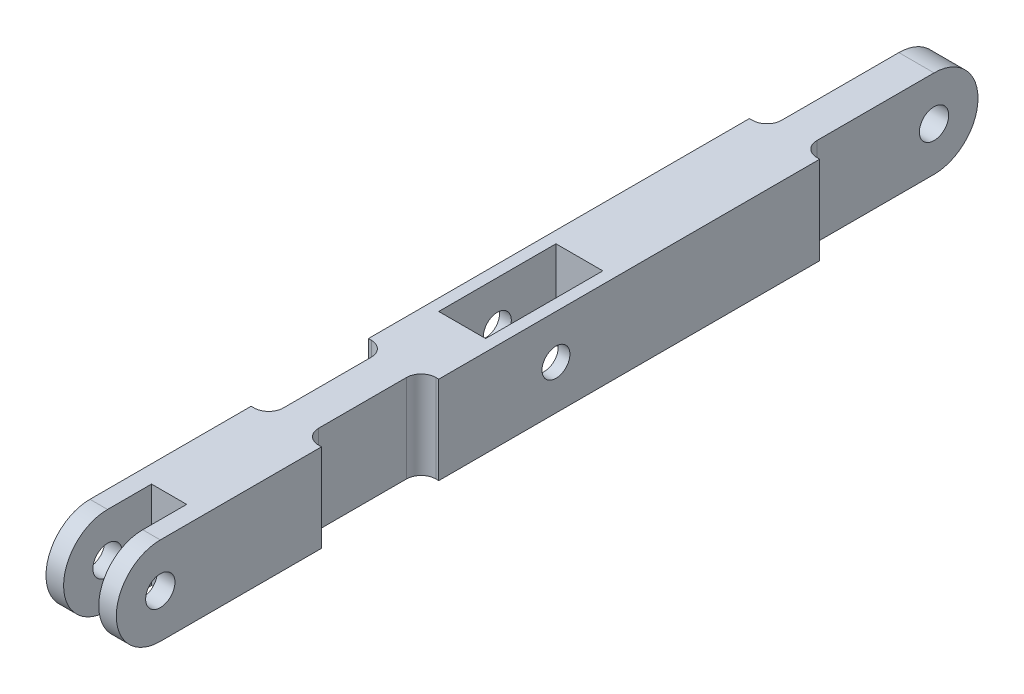
SolidWorks part; units mm, degrees
material "ABS P400"
ref_plane "Front Plane" through (0, 0, 0) normal (0, 0, 1) x (1, 0, 0)
ref_plane "Top Plane" through (0, 0, 0) normal (0, 1, 0) x (1, 0, 0)
ref_plane "Right Plane" through (0, 0, 0) normal (1, 0, 0) x (0, 0, -1)
sketch "Sketch1" plane through (0, 0, 0) normal (1, 0, 0) x (0, 0, -1)
  line L0 (-67.5, 0) -> (67.5, 0) construction
  line L1 (-67.5, 7.5) -> (67.5, 7.5)
  line L2 (-67.5, -7.5) -> (67.5, -7.5)
  arc A0 (-67.5, 7.5) -> (-67.5, -7.5) centre (-67.5, 0) ccw
  arc A1 (67.5, -7.5) -> (67.5, 7.5) centre (67.5, 0) ccw
  circle A2 centre (-67.5, 0) radius 2.5
  circle A3 centre (0, 0) radius 2.3813
  circle A4 centre (67.5, 0) radius 2.5
  point P2 (0, 0)
  dimension "D3" = 4.7625
  dimension "D4" = 5
  dimension "D5" = 5
  dimension "D1" = 67.5
  dimension "D2" = 15
extrude "BASE" add sketch "Sketch1" along normal mid plane 12
sketch "Sketch2" plane through (0, 0, 0) normal (0, 1, 0) x (1, 0, 0)
  line L0 (0, -105.1442) -> (0, -44.8558) construction
  line L1 (-3, -90) -> (-3, -60)
  line L2 (-3, -90) -> (3, -90)
  line L3 (-3, -60) -> (3, -60)
  line L4 (3, -90) -> (3, -60)
  line L5 (-3, -90) -> (3, -60) construction
  line L6 (-3, -60) -> (3, -90) construction
  line L8 (-6, 67.5) -> (-6, -67.5) construction
  line L9 (-9, -40) -> (-3, -40)
  line L10 (-9, -40) -> (-9, -20)
  line L11 (-9, -20) -> (-3, -20)
  line L12 (-3, -40) -> (-3, -20)
  line L13 (-9, -40) -> (-3, -20) construction
  line L14 (-9, -20) -> (-3, -40) construction
  line L15 (9, -40) -> (3, -20) construction
  line L16 (9, -20) -> (3, -40) construction
  line L17 (9, -40) -> (9, -20)
  line L18 (9, -40) -> (3, -40)
  line L19 (3, -40) -> (3, -20)
  line L20 (9, -20) -> (3, -20)
  line L21 (6, 67.5) -> (6, -67.5) construction
  line L22 (9, 45) -> (3, 45)
  line L23 (9, 45) -> (9, 75)
  line L24 (9, 75) -> (3, 75)
  line L25 (3, 45) -> (3, 75)
  line L26 (9, 45) -> (3, 75) construction
  line L27 (9, 75) -> (3, 45) construction
  line L28 (-9, 45) -> (-3, 75) construction
  line L29 (-9, 75) -> (-3, 45) construction
  line L30 (-9, 45) -> (-9, 75)
  line L31 (-9, 45) -> (-3, 45)
  line L32 (-3, 45) -> (-3, 75)
  line L33 (-9, 75) -> (-3, 75)
  line L37 (6, -67.5) -> (-6, -67.5) construction
  line L40 (-6.6, 0) -> (6.6, 0) construction
  line L41 (6, 75) -> (-6, 75) construction
  line L43 (-4, -10) -> (4, -10)
  line L44 (-4, -10) -> (-4, 10)
  line L45 (-4, 10) -> (4, 10)
  line L46 (4, -10) -> (4, 10)
  line L47 (-4, -10) -> (4, 10) construction
  line L48 (-4, 10) -> (4, -10) construction
  point P4 (0, -75)
  point P6 (-6, -30)
  point P17 (6, -30)
  point P20 (6, 60)
  point P29 (-6, 60)
  point P47 (0, 0)
  dimension "D1" = 6
  dimension "D2" = 15
  dimension "D3" = 6
  dimension "D4" = 20
  dimension "D5" = 20
  dimension "D6" = 6
  dimension "D7" = 30
  dimension "D8" = 8
  dimension "D9" = 20
extrude "All_Cuts" cut sketch "Sketch2" against normal through all both and the other way through all
fillet "Fillet1" radius 2.5 6 edges at (3, 0, -45) (3, 0, 40) (3, 0, 20) (-3, 0, 40) (-3, 0, 20) (-3, 0, -45)
